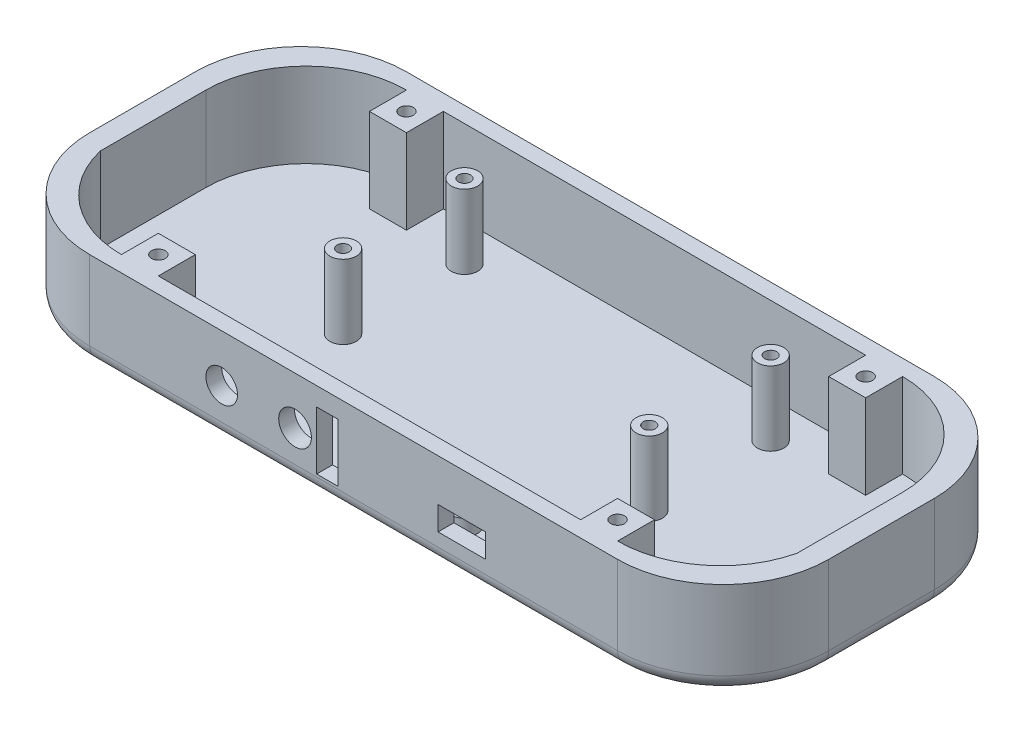
SolidWorks part; units mm, degrees
ref_plane "Front Plane" through (0, 0, 0) normal (0, 0, 1) x (1, 0, 0)
ref_plane "Top Plane" through (0, 0, 0) normal (0, 1, 0) x (1, 0, 0)
ref_plane "Right Plane" through (0, 0, 0) normal (1, 0, 0) x (0, 0, -1)
sketch "Sketch1" plane through (0, 0, 0) normal (0, 1, 0) x (1, 0, 0)
  line L0 (70, 10) -> (70, -10)
  line L1 (-50, 30) -> (50, 30)
  line L2 (-70, 10) -> (-70, -10)
  line L3 (-50, -30) -> (50, -30)
  line L5 (-50, 30) -> (50, -30) construction
  line L6 (-50, -30) -> (50, 30) construction
  arc A0 (-50, 30) -> (-70, 10) centre (-50, 10) ccw
  arc A1 (50, 30) -> (70, 10) centre (50, 10) cw
  arc A2 (-50, -30) -> (-70, -10) centre (-50, -10) cw
  arc A3 (50, -30) -> (70, -10) centre (50, -10) ccw
  point P0 (0, 0)
  dimension "D3" = 20
  dimension "D1" = 100
  dimension "D2" = 70
extrude "Boss-Extrude1" add sketch "Sketch1" along normal blind 2
sketch "Sketch2" plane through (0, 2, 0) normal (0, 1, 0) x (1, 0, 0)
  line L0 (-50, -30) -> (50, -30) construction
  line L1 (-47, 27) -> (47, 27)
  line L2 (-50, 30) -> (50, 30)
  line L3 (-47, -27) -> (47, -27)
  line L4 (70, 10) -> (70, -10)
  line L5 (-47, 27) -> (47, -27) construction
  line L6 (-47, -27) -> (47, 27) construction
  line L7 (-50, -30) -> (50, -30)
  line L8 (66, 8) -> (66, -12)
  line L9 (-50, 30) -> (50, -30) construction
  line L10 (-50, -30) -> (50, 30) construction
  line L11 (-70, 10) -> (-70, -10)
  line L13 (-66, 8) -> (-66, -12)
  arc A0 (-50, 30) -> (-70, 10) centre (-50, 10) ccw
  arc A1 (50, 30) -> (70, 10) centre (50, 10) cw
  arc A2 (-50, -30) -> (-70, -10) centre (-50, -10) cw
  arc A3 (50, -30) -> (70, -10) centre (50, -10) ccw
  arc A4 (47, 27) -> (66, 8) centre (47, 8) cw
  arc A5 (47, -27) -> (66, -12) centre (47, -7.4667) ccw
  arc A6 (-47, 27) -> (-66, 8) centre (-47, 8) ccw
  arc A7 (-47, -27) -> (-66, -12) centre (-47, -7.4667) cw
  point P0 (0, 0)
  point P8 (0, 0)
  line M6 (50, 30) -> (-50, 30)
  line M8 (-50, -30) -> (50, -30)
  dimension "D3" = 100
  dimension "D4" = 60
  dimension "D5" = 20
  dimension "D1" = 54
  dimension "D2" = 94
  dimension "D6" = 54
  dimension "D7" = 20
  dimension "D8" = 4
  dimension "D9" = 3
  dimension "D10" = 3
  dimension "D11" = 4
extrude "Boss-Extrude2" add sketch "Sketch2" along normal blind 16 contours L3 M8 | L1 M6 region at (0, 2, -28.4768)
sketch "Sketch12" plane through (0, 2, 0) normal (0, 1, 0) x (1, 0, 0)
  line L0 (-47, 27) -> (47, 27) construction
  line L1 (-47, 27) -> (-40, 27)
  line L2 (-47, 27) -> (-47, 20)
  line L3 (-47, 20) -> (-40, 20)
  line L4 (-40, 27) -> (-40, 20)
  line L5 (-47, -27) -> (-40, -27)
  line L6 (-47, -27) -> (-47, -20)
  line L7 (-47, -20) -> (-40, -20)
  line L8 (-40, -27) -> (-40, -20)
  line L9 (47, -27) -> (40, -27)
  line L10 (47, -27) -> (47, -20)
  line L11 (47, -20) -> (40, -20)
  line L12 (40, -27) -> (40, -20)
  line L13 (47, 27) -> (40, 27)
  line L14 (47, 27) -> (47, 20)
  line L15 (47, 20) -> (40, 20)
  line L16 (40, 27) -> (40, 20)
  line L17 (-47, -27) -> (47, -27) construction
  dimension "D1" = 7
  dimension "D2" = 7
  dimension "D3" = 7
  dimension "D4" = 7
  dimension "D5" = 7
  dimension "D6" = 7
  dimension "D7" = 7
  dimension "D8" = 7
  dimension "D9" = 0
  dimension "D10" = 0
  dimension "D11" = 0
  dimension "D12" = 0
  dimension "D13" = 0
  dimension "D14" = 0
extrude "Boss-Extrude5" add sketch "Sketch12" along normal blind 16
fillet "Fillet1" radius 3 8 edges at (-64.1421, 0, 24.1421) (-64.1421, 0, -24.1421) (-70, 0, 0) (0, 0, 30) (64.1421, 0, 24.1421) (70, 0, 0) (64.1421, 0, -24.1421) (0, 0, -30)
sketch "Sketch13" plane through (0, 18, 0) normal (0, 1, 0) x (1, 0, 0)
  line L0 (47, 20) -> (47, 27) construction
  line L1 (40, 20) -> (47, 20) construction
  line L2 (47, -27) -> (47, -20) construction
  line L3 (47, -20) -> (40, -20) construction
  line L4 (-40, -27) -> (-40, -20) construction
  line L5 (-40, -20) -> (-47, -20) construction
  line L6 (-47, 20) -> (-40, 20) construction
  line L7 (-47, 27) -> (-47, 20) construction
  circle A0 centre (-43.5, 23.5) radius 1.3
  circle A1 centre (-43.5, -23.5) radius 1.3
  circle A2 centre (43.5, -23.5) radius 1.3
  circle A3 centre (43.5, 23.5) radius 1.3
  dimension "D1" = 2.6
  dimension "D2" = 2.6
  dimension "D3" = 2.6
  dimension "D4" = 2.6
  dimension "D7" = 3.5
  dimension "D8" = 3.5
  dimension "D9" = 3.5
  dimension "D11" = 3.5
  dimension "D12" = 3.5
  dimension "D5" = 3.5
  dimension "D6" = 3.5
  dimension "D10" = 3.5
extrude "Cut-Extrude7" cut sketch "Sketch13" against normal through all
sketch "Sketch14" plane through (0, 2, 0) normal (0, 1, 0) x (1, 0, 0)
  line L1 (-40, 27) -> (40, 27) construction
  circle A0 centre (29, -3) radius 2.5
  circle A1 centre (29, 20) radius 2.5
  circle A2 centre (-29, 20) radius 2.5
  circle A3 centre (-29, -3) radius 2.5
  circle A4 centre (29, -3) radius 1.15
  circle A5 centre (29, 20) radius 1.15
  circle A6 centre (-29, 20) radius 1.15
  circle A7 centre (-29, -3) radius 1.15
  dimension "D1" = 5
  dimension "D2" = 5
  dimension "D3" = 5
  dimension "D4" = 5
  dimension "D6" = 29
  dimension "D7" = 29
  dimension "D8" = 29
  dimension "D9" = 58
  dimension "D10" = 58
  dimension "D11" = 7
  dimension "D12" = 23
  dimension "D13" = 2.3
  dimension "D14" = 2.3
  dimension "D15" = 2.3
  dimension "D16" = 2.3
  dimension "D5" = 29
extrude "Boss-Extrude6" add sketch "Sketch14" along normal blind 14
sketch "Sketch15" plane through (0, 2, 0) normal (0, 1, 0) x (1, 0, 0)
  line L1 (-40, -27) -> (40, -27) construction
  circle A0 centre (29, -23) radius 2.5
  circle A1 centre (14, -23) radius 2.5
  circle A2 centre (29, -23) radius 1.3
  circle A3 centre (14, -23) radius 1.3
  dimension "D1" = 5
  dimension "D2" = 5
  dimension "D4" = 15
  dimension "D7" = 2.6
  dimension "D8" = 2.6
  dimension "D5" = 4
  dimension "D6" = 4
extrude "Boss-Extrude7" add sketch "Sketch15" along normal blind 3
sketch "Sketch16" plane through (0, 0, 27) normal (0, 0, -1) x (-1, 0, 0)
  line L0 (-40, 18) -> (-40, 2) construction
  line L1 (-25, 10) -> (-16, 10)
  line L2 (-25, 10) -> (-25, 5.5)
  line L3 (-25, 5.5) -> (-16, 5.5)
  line L4 (-16, 10) -> (-16, 5.5)
  line L5 (-25, 10) -> (-16, 5.5) construction
  line L6 (-25, 5.5) -> (-16, 10) construction
  line L7 (40, 2) -> (-40, 2) construction
  point P0 (-20.5, 7.75)
  dimension "D1" = 15
  dimension "D2" = 9
  dimension "D3" = 4.5
  dimension "D4" = 3.5
extrude "Cut-Extrude8" cut sketch "Sketch16" against normal through all
sketch "Sketch17" plane through (0, 0, 0) normal (0, -1, 0) x (1, 0, 0)
  circle A0 centre (-43.5, 23.5) radius 3.25
  circle A1 centre (43.5, 23.5) radius 3.25
  circle A2 centre (43.5, -23.5) radius 3.25
  circle A3 centre (-43.5, -23.5) radius 3.25
  dimension "D1" = 6.5
  dimension "D2" = 6.5
  dimension "D3" = 6.5
  dimension "D4" = 6.5
extrude "Cut-Extrude9" cut sketch "Sketch17" against normal blind 13
sketch "Sketch19" plane through (0, 0, 27) normal (0, 0, -1) x (-1, 0, 0)
  line L0 (-16, 5.5) -> (-16, 10) construction
  line L1 (40, 2) -> (-40, 2) construction
  circle A0 centre (-1, 9) radius 2.5
  circle A1 centre (34, 9) radius 2.5
  circle A2 centre (-1, 9) radius 1.15
  circle A3 centre (34, 9) radius 1.15
  dimension "D1" = 5
  dimension "D2" = 5
  dimension "D3" = 35
  dimension "D6" = 7
  dimension "D7" = 2.3
  dimension "D8" = 2.3
  dimension "D4" = 15
  dimension "D5" = 7
extrude "Boss-Extrude8" add sketch "Sketch19" along normal blind 2.5
sketch "Sketch20" plane through (0, 0, 27) normal (0, 0, -1) x (-1, 0, 0)
  line L0 (40, 2) -> (-40, 2) construction
  line L1 (3, 14.5) -> (7, 14.5)
  line L2 (3, 14.5) -> (3, 3.5)
  line L3 (3, 3.5) -> (7, 3.5)
  line L4 (7, 14.5) -> (7, 3.5)
  line L5 (3, 14.5) -> (7, 3.5) construction
  line L6 (3, 3.5) -> (7, 14.5) construction
  circle A0 centre (-1, 9) radius 1.15 construction
  circle A1 centre (11.1, 9) radius 3.1
  circle A2 centre (25, 9) radius 3
  circle A3 centre (34, 9) radius 1.15 construction
  point P0 (5, 9)
  dimension "D2" = 0
  dimension "D4" = 4
  dimension "D5" = 6.2
  dimension "D6" = 7
  dimension "D7" = 12.1
  dimension "D8" = 7
  dimension "D9" = 6
  dimension "D10" = 9
  dimension "D1" = 11
  dimension "D3" = 4
extrude "Cut-Extrude10" cut sketch "Sketch20" against normal blind 5
sketch "Sketch21" plane through (0, 0, 24.5) normal (0, 0, -1) x (-1, 0, 0)
  circle A0 centre (-1, 9) radius 1.15
extrude "Cut-Extrude11" cut sketch "Sketch21" against normal blind 3.5
sketch "Sketch22" plane through (0, 0, 24.5) normal (0, 0, -1) x (-1, 0, 0)
  circle A0 centre (34, 9) radius 1.15
extrude "Cut-Extrude12" cut sketch "Sketch22" against normal blind 3.5
